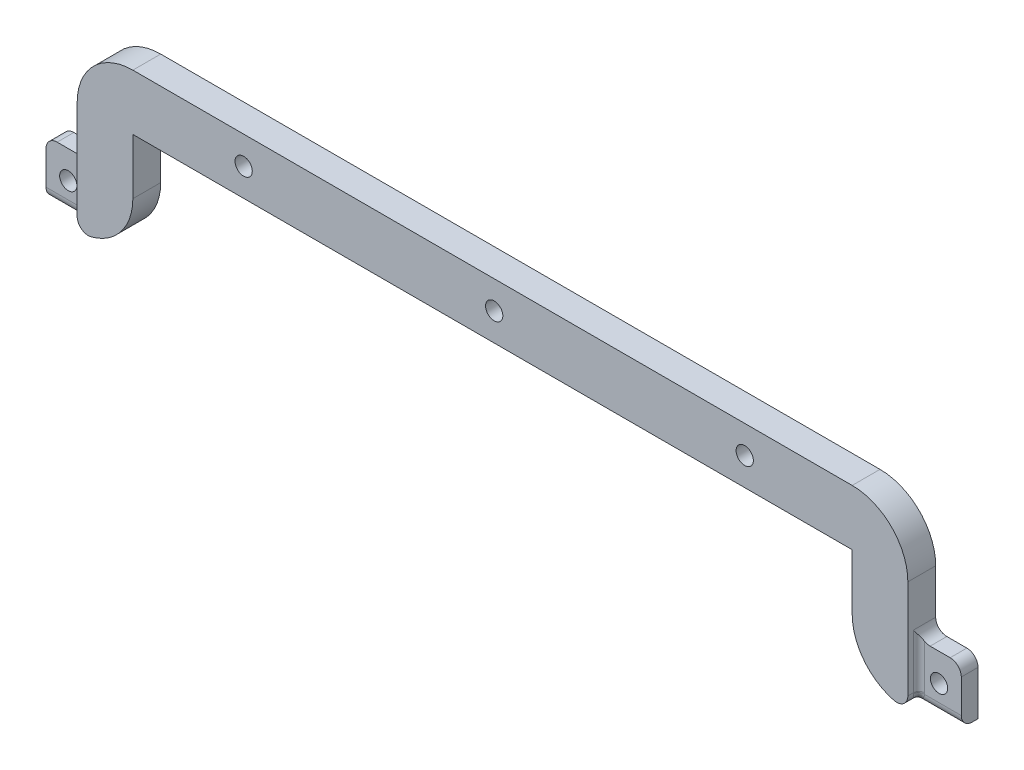
SolidWorks part; units mm, degrees
material "PUR"
ref_plane "Front Plane" through (0, 0, 0) normal (0, 0, 1) x (1, 0, 0)
ref_plane "Top Plane" through (0, 0, 0) normal (0, 1, 0) x (1, 0, 0)
ref_plane "Right Plane" through (0, 0, 0) normal (1, 0, 0) x (0, 0, -1)
sketch "Sketch2" plane through (0, 0, 0) normal (0, 0, 1) x (1, 0, 0)
  line L0 (7.7754, 8.7481) -> (7.7754, -4.7183) construction
  line L1 (-74.4246, -1.2519) -> (-56.8246, -1.2519)
  line L2 (-74.4246, -1.2519) -> (-74.4246, 8.7481)
  line L3 (-74.4246, 8.7481) -> (-66.8246, 8.7481)
  line L4 (89.9754, -1.2519) -> (89.9754, 8.7481)
  line L5 (-66.8246, 8.7481) -> (-66.8246, 28.7481)
  line L6 (-66.8246, 28.7481) -> (82.3754, 28.7481)
  line L7 (82.3754, 28.7481) -> (82.3754, 8.7481)
  line L8 (-56.8246, -1.2519) -> (-56.8246, 18.7481)
  line L9 (72.3754, -1.2519) -> (89.9754, -1.2519)
  line L10 (72.3754, 18.7481) -> (72.3754, -1.2519)
  line L11 (-56.8246, 18.7481) -> (72.3754, 18.7481)
  line L13 (82.3754, 8.7481) -> (89.9754, 8.7481)
  circle A0 centre (-70.4246, 3.7481) radius 1.55
  circle A1 centre (85.9754, 3.7481) radius 1.55
  dimension "D3" = 3.1
  dimension "D11" = 4
  dimension "D1" = 164.4
  dimension "D2" = 10
  dimension "D4" = 4
  dimension "D5" = 5
  dimension "D6" = 7.6
  dimension "D7" = 7.6
  dimension "D8" = 10
  dimension "D9" = 10
  dimension "D10" = 20
  dimension "D12" = 20
extrude "Boss-Extrude1" add sketch "Sketch2" along normal blind 5
sketch "Sketch3" plane through (0, 0, 5) normal (0, 0, 1) x (1, 0, 0)
  line L0 (-74.4246, 23.7481) -> (-59.2246, 23.7481) construction
  line L3 (82.3754, 28.7481) -> (-66.8246, 28.7481) construction
  circle A0 centre (-70.4246, 3.7481) radius 1.55 construction
  circle A2 centre (-36.9246, 23.7481) radius 1.55
  circle A4 centre (8.0754, 23.7481) radius 1.55
  circle A5 centre (53.0754, 23.7481) radius 1.55
  dimension "D1" = 3.1
  dimension "D2" = 33.5
  dimension "D4" = 5
  dimension "D5" = 5
  dimension "D3" = 3
extrude "Cut-Extrude1" cut sketch "Sketch3" against normal up to next
fillet "Fillet1" radius 10 4 edges at (72.3754, -1.2519, 2.5) (-56.8246, -1.2519, 2.5) (82.3754, 28.7481, 2.5) (-66.8246, 28.7481, 2.5)
sketch "Sketch4" plane through (0, 0, 5) normal (0, 0, 1) x (1, 0, 0)
  line L1 (89.9754, 8.7481) -> (82.3754, 8.7481)
  line L2 (89.9754, 8.7481) -> (89.9754, -1.2519)
  line L3 (89.9754, -1.2519) -> (82.3754, -1.2519)
  line L4 (82.3754, 8.7481) -> (82.3754, -1.2519)
  line L6 (-74.4246, 8.7481) -> (-66.8246, 8.7481)
  line L7 (-74.4246, 8.7481) -> (-74.4246, -1.2519)
  line L8 (-74.4246, -1.2519) -> (-66.8246, -1.2519)
  line L9 (-66.8246, 8.7481) -> (-66.8246, -1.2519)
  arc A0 (72.3754, 8.7481) -> (82.3754, -1.2519) centre (82.3754, 8.7481) ccw construction
  arc A1 (-66.8246, -1.2519) -> (-56.8246, 8.7481) centre (-66.8246, 8.7481) ccw construction
extrude "Cut-Extrude3" cut sketch "Sketch4" against normal blind 2
fillet "Fillet2" radius 2 4 edges at (-70.6246, -1.2519, 3) (86.1754, -1.2519, 3) (82.3754, -1.2519, 4) (-66.8246, -1.2519, 4)
fillet "Fillet4" radius 2 4 edges at (82.3754, 8.7481, 1.5) (-66.8246, 8.7481, 1.5) (-74.4246, 8.7481, 1.5) (89.9754, 8.7481, 1.5)
fillet "Fillet5" radius 1 6 edges at (-65.9267, -0.6668, 2.3694) (-66.8205, 0.8748, 3) (-66.8246, 5.8751, 3) (81.4776, -0.6668, 2.3694) (82.3714, 0.8748, 3) (82.3754, 5.8751, 3)
